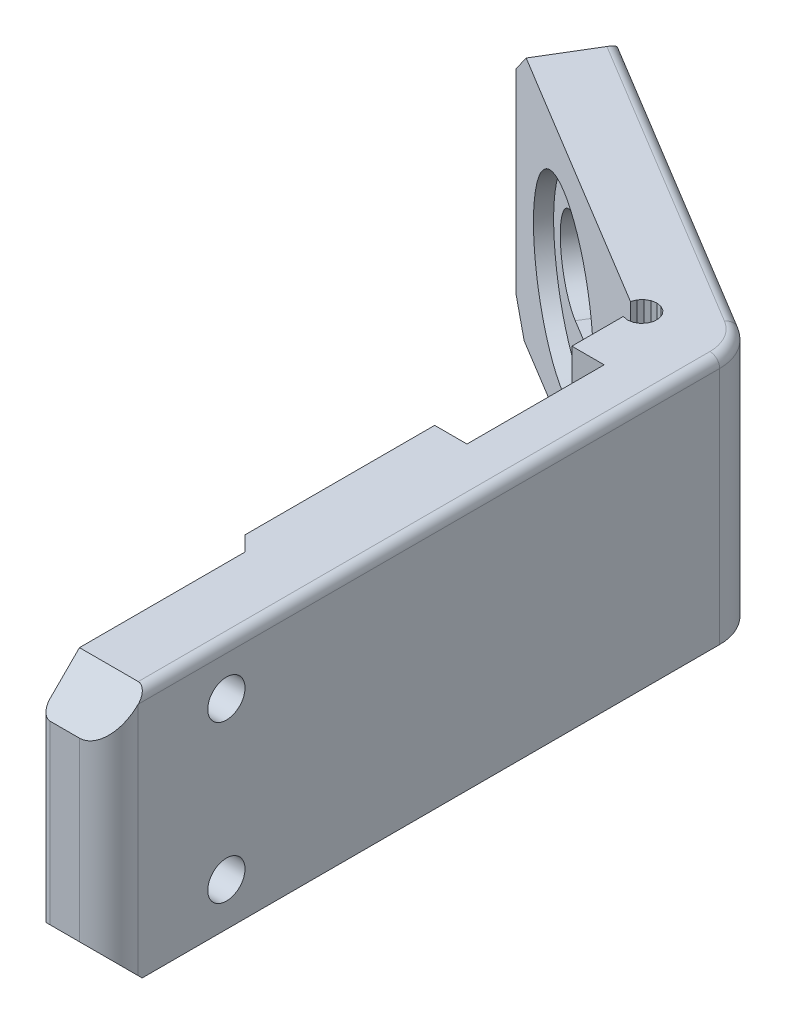
SolidWorks part; units mm, degrees
ref_plane "Front Plane" through (0, 0, 0) normal (0, 0, 1) x (1, 0, 0)
ref_plane "Top Plane" through (0, 0, 0) normal (0, 1, 0) x (1, 0, 0)
ref_plane "Right Plane" through (0, 0, 0) normal (1, 0, 0) x (0, 0, -1)
ref_plane "PY -20.700" through (0, -20.7, 0) normal (0, 1, 0) x (1, 0, 0)
sketch "leg and pad sketch" plane through (0, -20.7, 0) normal (0, 1, 0) x (1, 0, 0)
  line L0 (-0.5513, 30.3327) -> (-0.3673, 30.8194)
  line L1 (-0.3673, 30.8194) -> (-0.028, 31.2139)
  line L2 (-0.028, 31.2139) -> (0.4256, 31.4688)
  line L3 (0.4256, 31.4688) -> (0.939, 31.5534)
  line L4 (0.939, 31.5534) -> (1.4504, 31.4576)
  line L5 (1.4504, 31.4576) -> (1.8983, 31.1928)
  line L6 (1.8983, 31.1928) -> (2.2288, 30.7909)
  line L7 (2.2288, 30.7909) -> (2.4021, 30.3003)
  line L8 (2.4021, 30.3003) -> (2.3973, 29.78)
  line L9 (2.3973, 29.78) -> (2.2152, 29.2926)
  line L10 (2.2152, 29.2926) -> (1.8775, 28.8968)
  line L11 (1.8775, 28.8968) -> (1.4248, 28.6402)
  line L12 (1.4248, 28.6402) -> (0.9118, 28.5536)
  line L13 (0.9118, 28.5536) -> (0.4, 28.6475)
  line L14 (0.4, 28.6475) -> (0.4, -9.98)
  line L15 (0.4, -9.98) -> (1.92, -11.5)
  line L16 (1.92, -11.5) -> (1.92, -32.37)
  line L17 (1.92, -32.37) -> (8.92, -32.37)
  line L18 (8.92, -32.37) -> (8.92, 32.7926)
  line L19 (8.92, 32.7926) -> (-27.2048, 54.5947)
  line L20 (-27.2048, 54.5947) -> (-30.8218, 48.6015)
  line L21 (-30.8218, 48.6015) -> (-0.5513, 30.3327)
extrude "leg and pad" add sketch "leg and pad sketch" along normal mid plane 26
ref_plane "PX 1.350" through (1.35, 0, 0) normal (1, 0, 0) x (0, 0, -1)
sketch "screw head relief sketch" plane through (1.35, 0, 0) normal (1, 0, 0) x (0, 0, -1)
  line L0 (23.4, -12.7) -> (23.4, -6.7)
  line L1 (23.4, -6.7) -> (9.4, -6.7)
  line L2 (9.4, -6.7) -> (9.4, -12.7)
  line L3 (9.4, -12.7) -> (23.4, -12.7)
extrude "screw head relief" cut sketch "screw head relief sketch" against normal mid plane 4.7
sketch "insert flange relief sketch" plane through (0, -20.7, 0) normal (0, 1, 0) x (1, 0, 0)
  line L0 (-18.3249, 39.8914) -> (-17.0331, 42.0318)
  line L1 (-17.0331, 42.0318) -> (-9.3276, 37.3814)
  line L2 (-9.3276, 37.3814) -> (-10.6194, 35.241)
  line L3 (-10.6194, 35.241) -> (-18.3249, 39.8914)
revolve "insert flange relief" cut sketch "insert flange relief sketch" angle 360 about L0
sketch "M6 slot end 1 sketch" plane through (0, -20.7, 0) normal (0, 1, 0) x (1, 0, 0)
  line L0 (-20.4653, 41.1832) -> (-15.8149, 48.8886)
  line L1 (-15.8149, 48.8886) -> (-11.9621, 46.5634)
  line L2 (-11.9621, 46.5634) -> (-16.6125, 38.858)
  line L3 (-16.6125, 38.858) -> (-20.4653, 41.1832)
revolve "M6 slot end 1" cut sketch "M6 slot end 1 sketch" angle 360 about L0
sketch "M6 slot end 2 sketch" plane through (0, -20.7, 0) normal (0, 1, 0) x (1, 0, 0)
  line L0 (-16.1845, 38.5996) -> (-11.5341, 46.3051)
  line L1 (-11.5341, 46.3051) -> (-7.6813, 43.9799)
  line L2 (-7.6813, 43.9799) -> (-12.3317, 36.2744)
  line L3 (-12.3317, 36.2744) -> (-16.1845, 38.5996)
revolve "M6 slot end 2" cut sketch "M6 slot end 2 sketch" angle 360 about L0
sketch "M6 slot middle sketch" plane through (0, -20.7, 0) normal (0, 1, 0) x (1, 0, 0)
  line L0 (-16.1845, 38.5996) -> (-20.4653, 41.1832)
  line L1 (-20.4653, 41.1832) -> (-15.8149, 48.8886)
  line L2 (-15.8149, 48.8886) -> (-11.5341, 46.3051)
  line L3 (-11.5341, 46.3051) -> (-16.1845, 38.5996)
extrude "M6 slot middle" cut sketch "M6 slot middle sketch" against normal mid plane 9
ref_plane "PX 5.420" through (5.42, 0, 0) normal (1, 0, 0) x (0, 0, -1)
sketch "screw holes sketch" plane through (5.42, 0, 0) normal (1, 0, 0) x (0, 0, -1)
  circle A0 centre (-20.375, -28.7) radius 1.9
  circle A1 centre (-20.375, -12.7) radius 1.9
extrude "screw holes" cut sketch "screw holes sketch" against normal mid plane 9
chamfer "leg top corners" distance 4 angle 45 2 edges at (5.42, -7.7, 32.37) (5.42, -33.7, 32.37) tangent propagation no
chamfer "pad end corners" distance 4 angle 45 2 edges at (-29.0133, -7.7, -51.5981) (-29.0133, -33.7, -51.5981) tangent propagation no
fillet "outside of the bend" radius 5 1 edges at (8.92, -20.7, -32.7926) tangent propagation no
fillet "leg top outer edge" radius 3 1 edges at (8.92, -20.7, 32.37) tangent propagation no
fillet "pad end outer edge" radius 3 1 edges at (-27.2048, -20.7, -54.5947) tangent propagation no
fillet "leg top inner edge" radius 1 1 edges at (1.92, -20.7, 32.37) tangent propagation no
fillet "pad end inner edge" radius 1 1 edges at (-30.8218, -20.7, -48.6015) tangent propagation no
chamfer "bed face chamfer" distance 0.6 angle 45 6 edges at (-13.9742, -33.7, -38.4337) (-8.6383, -33.7, -43.3894) (1.92, -33.7, 19.935) (0.4, -33.7, -9.3337) (8.2742, -33.7, -32.4281) (8.92, -33.7, -0.8001)
fillet "top face edge" radius 1 3 edges at (-8.6383, -7.7, -43.3894) (8.2742, -7.7, -32.4281) (8.92, -7.7, -0.8001)
equation "\"diffL\" = 608.8mm"
equation "\"diffW\" = 329.4mm"
equation "\"diffT\" = 2.9mm"
equation "\"chanSlotW\" = 12.9mm"
equation "\"chanSlotDepth\" = 11.13mm"
equation "\"chanFloor\" = 1.57mm"
equation "\"chanLeg\" = 12.7mm"
equation "\"lightL\" = 605mm"
equation "\"lightW\" = 331mm"
equation "\"lightH\" = 92mm"
equation "\"lightSideFlat\" = 30mm"
equation "\"lightSlopeLen\" = 33.1mm"
equation "\"lightWingDepth\" = 47.9mm"
equation "\"lightWingFlat\" = 90.2mm"
equation "\"lightChanW\" = 99.6mm"
equation "\"lightChanStand\" = 44.1mm"
equation "\"insFlangeD\" = 12.3mm"
equation "\"insFromEnd\" = 20.7mm"
equation "\"insUpSlope\" = 20.8mm"
equation "\"gaugeH\" = 10mm"
equation "\"gaugeStepLen\" = 14mm"
equation "\"gaugeStepW0\" = 13.1mm"
equation "\"gaugeStepDW\" = 0.2mm"
equation "\"gaugeSteps\" = 5mm"
equation "\"gaugeHandleLen\" = 30mm"
equation "\"gaugeHandleW\" = 24mm"
equation "\"gaugeSlot0\" = 3mm"
equation "\"gaugeSlotD\" = 0.1mm"
equation "\"gaugeSlotDepth\" = 8mm"
equation "\"gap\" = 25.4mm"
equation "\"edgeL\" = 1mm"
equation "\"edgeW\" = 0.75mm"
equation "\"proud\" = 1.5mm"
equation "\"seatClr\" = 0.15mm"
equation "\"tongueClrZ\" = 0.1mm"
equation "\"tongueClrX\" = 0.25mm"
equation "\"tongueLen\" = 30mm"
equation "\"armSide\" = 45mm"
equation "\"armEnd\" = 20mm"
equation "\"cornerCham\" = 3mm"
equation "\"brkW\" = 26mm"
equation "\"brkT\" = 7mm"
equation "\"brkSeatClr\" = 0.2mm"
equation "\"brkScrewSpan\" = 16mm"
equation "\"pilotD\" = 2.7mm"
equation "\"pilotDepth\" = 10mm"
equation "\"screwClrD\" = 3.9mm"
equation "\"jogBelow\" = 4mm"
equation "\"padT\" = 7mm"
equation "\"padLen\" = 31mm"
equation "\"m6Clr\" = 7mm"
equation "\"m6Slot\" = 3mm"
equation "\"flangeRelD\" = 17mm"
equation "\"flangeRelDepth\" = 1.5mm"
equation "\"relLen\" = 7mm"
equation "\"relDepth\" = 4mm"
equation "\"relLand\" = 2mm"
equation "\"knockN\" = 100mm"
equation "\"petgcfE\" = 3000mm"
equation "\"mockExtent\" = 110mm"
equation "\"relZnear\" = 9.4mm"
equation "\"relZfar\" = 23.4mm"
equation "\"headD\" = 8mm"
equation "\"headH\" = 2.5mm"
equation "\"headFromEnd\" = 6.8mm"
equation "\"headBack\" = 16.4mm"
equation "\"sideClr\" = 0.4mm"
equation "\"cornerRelR\" = 1.5mm"
equation "\"cornerRelBack\" = 0.6mm"
equation "\"endHeadH\" = 2.8mm"
equation "\"footClr\" = 1.2mm"
equation "\"footEndClr\" = 3.5mm"
equation "\"footLift\" = 6mm"
equation "\"footBlockClr\" = 0.5mm"
equation "\"footBack\" = 50mm"
equation "\"footFwd\" = 10mm"
equation "\"footBraceEnd\" = 3mm"
equation "\"footLoadN\" = 25mm"
equation "\"spacerLen\" = 60mm"
equation "\"spacerShort\" = 0.5mm"
equation "\"spacerCham\" = 0.8mm"
equation "\"spacerPerSide\" = 3mm"
equation "\"spacerPerEnd\" = 1mm"
equation "\"toolR\" = 9mm"
equation "\"visR\" = 4mm"
equation "\"edgeR\" = 1mm"
equation "\"bendOutR\" = 5mm"
equation "\"insideR\" = 2.5mm"
equation "\"footCornerR\" = 10mm"
equation "\"footFrontR\" = 8mm"
equation "\"braceKinkR\" = 12mm"
equation "\"bedCham\" = 1mm"
equation "\"bedChamSmall\" = 0.6mm"
equation "\"soleTopR\" = 2mm"
equation "\"cornerR\" = 6mm"
equation "\"rimInR\" = 1mm"
equation "\"insFlangeH\" = 1mm"
equation "\"insHoleFinishD\" = 4.5mm"
equation "\"insLen\" = 6.4mm"
